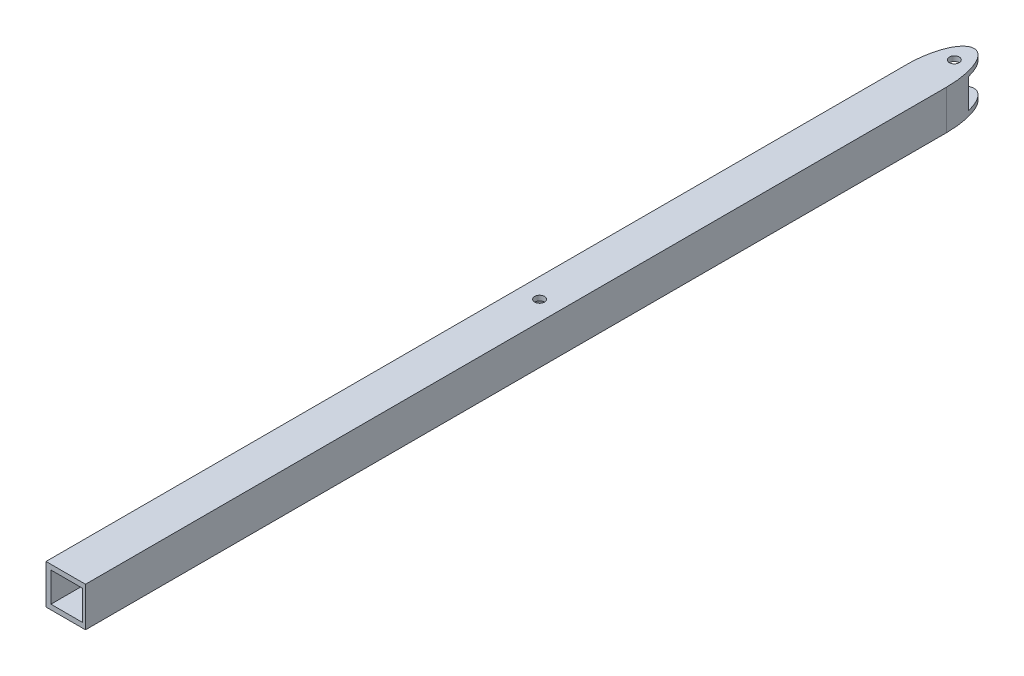
SolidWorks part; units mm, degrees
ref_plane "Front Plane" through (0, 0, 0) normal (0, 0, 1) x (1, 0, 0)
ref_plane "Top Plane" through (0, 0, 0) normal (0, 1, 0) x (1, 0, 0)
ref_plane "Right Plane" through (0, 0, 0) normal (1, 0, 0) x (0, 0, -1)
sketch "Sketch1" plane through (0, 0, 0) normal (0, 0, 1) x (1, 0, 0)
  line L1 (0, 0) -> (25.4, 0)
  line L2 (0, 0) -> (0, 25.4)
  line L3 (0, 25.4) -> (25.4, 25.4)
  line L4 (25.4, 0) -> (25.4, 25.4)
  dimension "D1" = 25.4
  dimension "D2" = 25.4
extrude "Boss-Extrude2" add sketch "Sketch1" along normal blind 584.2 contours L3 L4 L1 L2
sketch "Sketch2" plane through (0, 0, 0) normal (0, 0, -1) x (-1, 0, 0)
  line L0 (-23.4778, 22.225) -> (-3.175, 22.225)
  line L1 (-23.4778, 22.225) -> (-23.4778, 3.175)
  line L2 (-23.4778, 3.175) -> (-3.175, 3.175)
  line L3 (-3.175, 22.225) -> (-3.175, 3.175)
  line L4 (0, 0) -> (0, 25.4) construction
  line L5 (0, 0) -> (-25.4, 0) construction
  dimension "D1" = 3.175
  dimension "D2" = 3.175
extrude "Cut-Extrude1" cut sketch "Sketch2" against normal through all
sketch "Sketch3" plane through (0, 25.4, 0) normal (0, 1, 0) x (1, 0, 0)
  line L4 (0, 0) -> (25.4, 0) construction
  line L5 (12.7, 0) -> (25.4, 0)
  line L6 (25.4, 0) -> (25.4, -30.4659)
  line L7 (12.7, 0) -> (0, 0)
  line L8 (0, 0) -> (0, -30.4659)
  ellipse E0 centre (12.7, -30.4659) end of major axis (12.7, 0) minor radius 12.7 (25.4, -30.4659) -> (0, -30.4659) ccw
  line M2 (25.4, 0) -> (0, 0)
  line M3 (0, 0) -> (0, -584.2)
  line M5 (25.4, -584.2) -> (25.4, 0)
extrude "Cut-Extrude2" cut sketch "Sketch3" against normal through all contours E0 M2 M3 | E0 M5 M2 region at (2.8368, 25.4, 6.8051) region at (22.5632, 25.4, 6.8051)
sketch "Sketch4" plane through (0, 25.4, 0) normal (0, 1, 0) x (1, 0, 0)
  line L0 (25.4, -584.2) -> (0, -584.2)
  circle A1 centre (12.7, -279.4) radius 3.175
  point P17 (0, 0)
  dimension "D3" = 6.35
  dimension "D4" = 304.8
sketch "Sketch6" plane through (0, 25.4, 0) normal (0, 1, 0) x (1, 0, 0)
  line L0 (0, 0) -> (25.4, 0)
  circle A0 centre (12.7, -12.7) radius 3.175
  circle A1 centre (12.7, -1206.5) radius 3.175
  point P7 (12.7, 0)
  dimension "D2" = 6.35
  dimension "D3" = 12.7
  dimension "D4" = 6.35
  dimension "D5" = 1206.5
  dimension "D1" = 25.4
extrude "Cut-Extrude5" cut sketch "Sketch6" against normal through all contours A0
extrude "Cut-Extrude6" cut sketch "Sketch4" against normal through all contours A1
